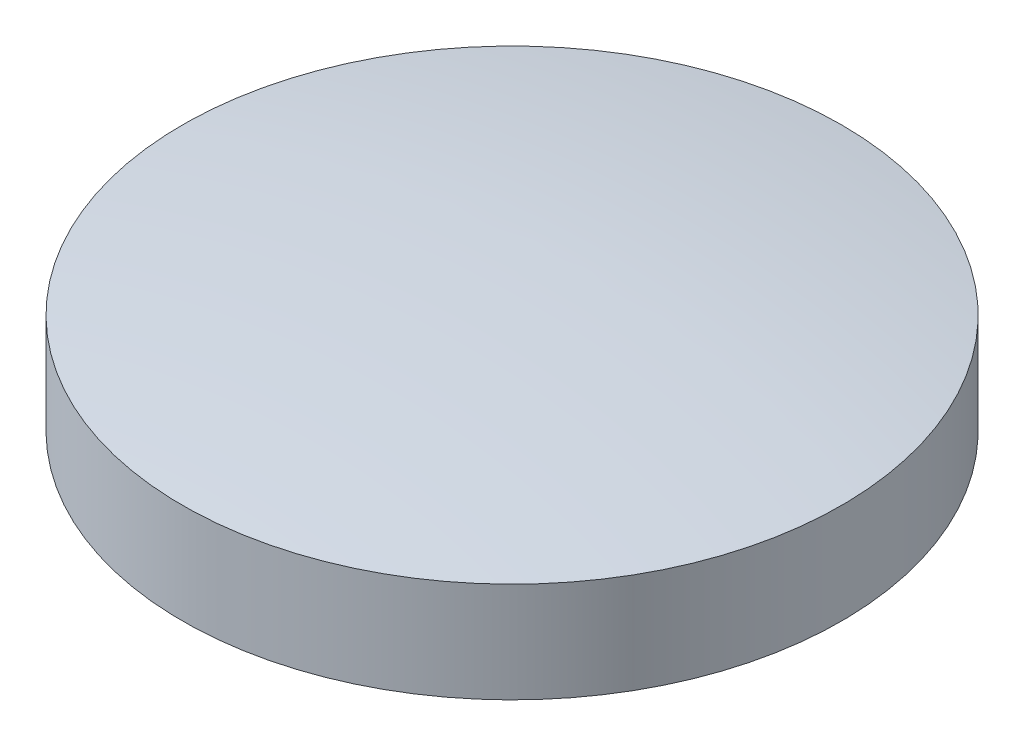
SolidWorks part; units mm, degrees
material "Glas"
ref_plane "Front" through (0, 0, 0) normal (0, 0, 1) x (1, 0, 0)
ref_plane "Top" through (0, 0, 0) normal (0, 1, 0) x (1, 0, 0)
ref_plane "Right" through (0, 0, 0) normal (1, 0, 0) x (0, 0, -1)
sketch "Skizze3" plane through (0, 0, 0) normal (1, 0, 0) x (0, 0, -1)
  line L0 (0, 0) -> (0, 14.7875) construction
  line L1 (0, 0) -> (25, 0)
  line L2 (25, 0) -> (25, 7.6005)
  line L4 (0, 9.605) -> (0, 0)
  arc A0 (25, 7.6005) -> (0, 9.605) centre (0, -147.2993) ccw
  dimension "D1" = 50
revolve "Rotation1" add sketch "Skizze3" angle 360 about L0
